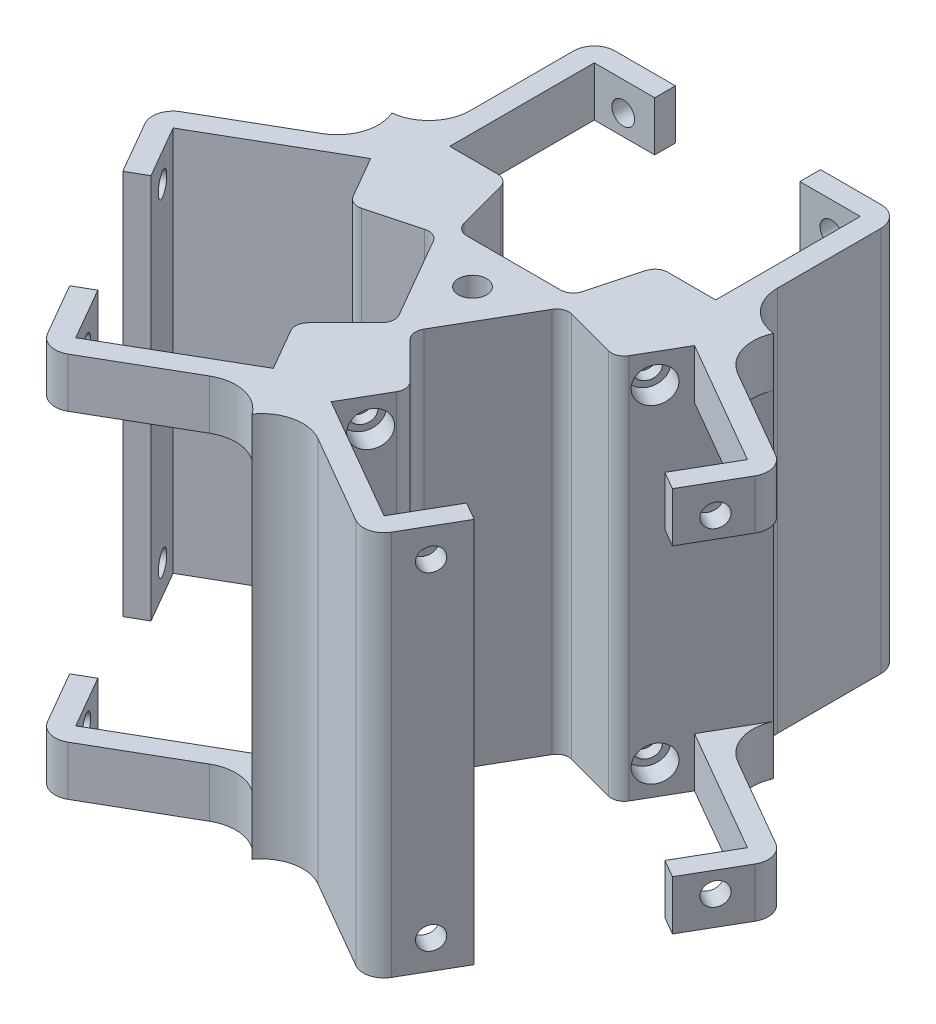
SolidWorks part; units mm, degrees
ref_plane "Alzado" through (0, 0, 0) normal (0, 0, 1) x (1, 0, 0)
ref_plane "Planta" through (0, 0, 0) normal (0, 1, 0) x (1, 0, 0)
ref_plane "Vista lateral" through (0, 0, 0) normal (1, 0, 0) x (0, 0, -1)
sketch "Croquis1" plane through (0, 0, 0) normal (0, 1, 0) x (1, 0, 0)
  line L0 (0, 50.8) -> (0, -50.8) construction
  line L1 (-50.8, 0) -> (50.8, 0) construction
  line L2 (0, 0) -> (-35.921, -35.921) construction
  line L3 (0, 0) -> (35.921, -35.921) construction
  line L10 (0, -17.5) -> (-15.1554, 8.75) construction
  line L11 (-15.1554, 8.75) -> (15.1554, 8.75) construction
  line L12 (15.1554, 8.75) -> (0, -17.5) construction
  line L13 (-1.2978, -16.7522) -> (-15.1813, 7.2027) construction
  line L14 (1.2978, -16.7522) -> (15.1813, 7.2027) construction
  line L15 (-13.8835, 9.4549) -> (13.8835, 9.4549) construction
  line L16 (1.6964, -16.0645) -> (13.335, -27.7031)
  line L17 (13.335, -27.7031) -> (0, -50.8)
  line L18 (0, -50.8) -> (-13.335, -27.7031)
  line L19 (-13.335, -27.7031) -> (-1.6964, -16.0645)
  line L20 (-17.3241, 25.4) -> (-13.0641, 9.5013)
  line L21 (-43.9941, 25.4) -> (-17.3241, 25.4)
  line L22 (-30.6591, 2.3031) -> (-43.9941, 25.4)
  line L23 (-14.7604, 6.5631) -> (-30.6591, 2.3031)
  line L24 (30.6591, 2.3031) -> (14.7604, 6.5631)
  line L25 (43.9941, 25.4) -> (30.6591, 2.3031)
  line L26 (17.3241, 25.4) -> (43.9941, 25.4)
  line L27 (13.0641, 9.5013) -> (17.3241, 25.4)
  line L28 (-14.7604, 6.5631) -> (-1.6964, -16.0645)
  line L29 (1.6964, -16.0645) -> (14.7604, 6.5631)
  line L30 (-13.0641, 9.5013) -> (13.0641, 9.5013)
  line L31 (-43.9941, 25.4) -> (0, -50.8) construction
  line L32 (43.9941, 25.4) -> (0, -50.8) construction
  line L33 (-43.9941, 25.4) -> (43.9941, 25.4) construction
  circle A0 centre (0, 0) radius 50.8 construction
  circle A7 centre (0, 0) radius 17.5 construction
  circle A8 centre (-13.8835, 7.9549) radius 1.5 construction
  circle A9 centre (13.8835, 7.9549) radius 1.5 construction
  circle A10 centre (0, -16) radius 1.5 construction
  arc A11 (-15.1813, 7.2027) -> (-13.8835, 9.4549) centre (-13.8835, 7.9549) cw construction
  arc A12 (15.1813, 7.2027) -> (13.8835, 9.4549) centre (13.8835, 7.9549) ccw construction
  arc A13 (1.2978, -16.7522) -> (-1.2978, -16.7522) centre (0, -16) cw construction
  arc A14 (-15.1813, 7.2027) -> (-13.8835, 9.4549) centre (-13.8835, 7.9549) cw construction
  arc A15 (13.8835, 9.4549) -> (15.1813, 7.2027) centre (13.8835, 7.9549) cw construction
  arc A16 (-1.2978, -16.7522) -> (1.2978, -16.7522) centre (0, -16) ccw construction
  circle A17 centre (0, 0) radius 76.2 construction
  point P45 (0, 0)
  dimension "D1" = 101.6
  dimension "D6" = 13.8835
  dimension "D9" = 3
  dimension "D5" = 3
  dimension "D4" = 35
  dimension "D10" = 152.4
  dimension "D2" = 45
  dimension "D3" = 45
  dimension "D7" = 26.67
extrude "Saliente-Extruir1" add sketch "Croquis1" along normal blind 88.9
sketch "Croquis4" plane through (0, 88.9, 0) normal (0, 1, 0) x (1, 0, 0)
  circle A0 centre (0, 0) radius 3.25
  dimension "D1" = 6.5
extrude "Cortar-Extruir1" cut sketch "Croquis4" against normal through all
fillet "Redondeo6" radius 3 5 edges at (-14.7604, 44.45, -6.5631) (1.6964, 44.45, 16.0645) (-1.6964, 44.45, 16.0645) (-13.0641, 44.45, -9.5013) (13.0641, 44.45, -9.5013)
fillet "Redondeo7" radius 3 6 edges at (-17.3241, 44.45, -25.4) (-30.6591, 44.45, -2.3031) (17.3241, 44.45, -25.4) (-13.335, 44.45, 27.7031) (30.6591, 44.45, -2.3031) (13.335, 44.45, 27.7031)
scale "Escala2" scale about centroid uniform scaling yes scale factor 1.05
sketch "Croquis9" plane through (0, 91.1225, 0) normal (0, 1, 0) x (1, 0, 0)
  line L9 (0, 76.2) -> (0, -76.2) construction
  line L10 (76.2, 0) -> (-76.2, 0) construction
  line L41 (-37.1934, 26.6702) -> (-37.1934, 61.6702)
  line L42 (-69.5041, -2.9545) -> (-39.1932, 14.5455)
  line L43 (-20.607, 26.6702) -> (-46.1934, 26.6702) construction
  line L44 (-32.1934, 66.6702) -> (-17.5643, 66.6702)
  line L45 (-17.5643, 66.6702) -> (-17.5643, 61.6702)
  line L46 (-17.5643, 61.6702) -> (-32.1934, 61.6702)
  line L47 (-32.1934, 61.6702) -> (-32.1934, 26.6702)
  line L48 (-32.1934, 26.6702) -> (-37.1934, 26.6702)
  line L49 (32.1934, 61.6702) -> (32.1934, 26.6702)
  line L50 (17.5643, 61.6702) -> (32.1934, 61.6702)
  line L51 (17.5643, 66.6702) -> (17.5643, 61.6702)
  line L52 (32.1934, 66.6702) -> (17.5643, 66.6702)
  line L53 (37.1934, 26.6702) -> (37.1934, 61.6702)
  line L54 (32.1934, 26.6702) -> (37.1934, 26.6702)
  line L55 (39.1937, 14.5452) -> (41.6937, 18.8753)
  line L56 (41.6937, 18.8753) -> (72.0046, 1.3753)
  line L57 (73.8347, -5.4548) -> (66.5202, -18.124)
  line L58 (66.5202, -18.124) -> (62.1901, -15.624)
  line L59 (62.1901, -15.624) -> (69.5046, -2.9548)
  line L60 (69.5046, -2.9548) -> (39.1937, 14.5452)
  line L61 (37.3112, -58.7154) -> (7.0003, -41.2154)
  line L62 (7.0003, -41.2154) -> (4.5003, -45.5455)
  line L63 (4.5003, -45.5455) -> (34.8112, -63.0455)
  line L64 (41.6414, -61.2154) -> (48.9559, -48.5462)
  line L65 (48.9559, -48.5462) -> (44.6258, -46.0462)
  line L66 (44.6258, -46.0462) -> (37.3112, -58.7154)
  line L79 (-39.1937, 14.5452) -> (-41.6937, 18.8753) [skipped]
  line L80 (-39.1932, 14.5455) -> (-41.6932, 18.8756)
  line L81 (-41.6937, 18.8753) -> (-72.0046, 1.3753) [skipped]
  line L83 (-41.6932, 18.8756) -> (-72.0041, 1.3756)
  line L85 (-69.5046, -2.9548) -> (-39.1937, 14.5452) [skipped]
  line L86 (-62.1901, -15.624) -> (-69.5046, -2.9548) [skipped]
  line L87 (-66.5202, -18.124) -> (-62.1901, -15.624) [skipped]
  line L88 (-73.8347, -5.4548) -> (-66.5202, -18.124) [skipped]
  line L89 (-73.8342, -5.4545) -> (-66.5197, -18.1237)
  line L90 (-66.5197, -18.1237) -> (-62.1896, -15.6237)
  line L91 (-62.1896, -15.6237) -> (-69.5041, -2.9545)
  line L92 (-46.1934, 26.6702) -> (-33.4002, 4.5117) construction
  line L93 (-7.0003, -41.2154) -> (-4.5003, -45.5455) [skipped]
  line L94 (-4.5003, -45.5455) -> (-34.8112, -63.0455) [skipped]
  line L95 (-41.6414, -61.2154) -> (-48.9559, -48.5462) [skipped]
  line L96 (-48.9559, -48.5462) -> (-44.6258, -46.0462) [skipped]
  line L97 (-44.6258, -46.0462) -> (-37.3112, -58.7154) [skipped]
  line L98 (-37.3112, -58.7154) -> (-7.0003, -41.2154) [skipped]
  line L99 (-6.9998, -41.2151) -> (-4.4998, -45.5452)
  line L100 (-4.4998, -45.5452) -> (-34.8107, -63.0452)
  line L101 (-41.6408, -61.2151) -> (-48.9554, -48.5459)
  line L102 (-48.9554, -48.5459) -> (-44.6253, -46.0459)
  line L103 (-44.6253, -46.0459) -> (-37.3107, -58.7151)
  line L104 (-37.3107, -58.7151) -> (-6.9998, -41.2151)
  line L105 (-12.7928, -31.1813) -> (0.0004, -53.3398) construction
  circle A0 centre (0, 0) radius 101.6 construction
  circle A1 centre (0, 0) radius 76.2 construction
  arc A8 (-37.1934, 61.6702) -> (-32.1934, 66.6702) centre (-32.1934, 61.6702) cw
  arc A9 (37.1934, 61.6702) -> (32.1934, 66.6702) centre (32.1934, 61.6702) ccw
  arc A10 (72.0046, 1.3753) -> (73.8347, -5.4548) centre (69.5046, -2.9548) cw
  arc A11 (34.8112, -63.0455) -> (41.6414, -61.2154) centre (37.3112, -58.7154) ccw
  arc A14 (-72.0046, 1.3753) -> (-73.8347, -5.4548) centre (-69.5046, -2.9548) ccw [skipped]
  arc A15 (-72.0041, 1.3756) -> (-73.8342, -5.4545) centre (-69.5041, -2.9545) ccw
  arc A16 (-34.8112, -63.0455) -> (-41.6414, -61.2154) centre (-37.3112, -58.7154) cw [skipped]
  arc A17 (-34.8107, -63.0452) -> (-41.6408, -61.2151) centre (-37.3107, -58.7151) cw
  point P55 (0.0002, 0.0003)
  point P56 (-1.3626, -0.7865)
  point P58 (0, 0)
  point P61 (0.0002, 0.0003)
  dimension "D1" = 152.4
  dimension "D2" = 203.2
  dimension "D3" = 5
  dimension "D9" = 2
  dimension "D4" = 9
  dimension "D5" = 35
  dimension "D6" = 3
  dimension "D7" = 2
sketch "Croquis12" plane through (0, 91.1225, 0) normal (0, 1, 0) x (1, 0, 0)
  line L0 (0, 101.6) -> (0, -101.6) construction
  circle A0 centre (0, 0) radius 76.2 construction
  circle A1 centre (0, 0) radius 101.6 construction
  dimension "D1" = 152.4
  dimension "D2" = 203.2
extrude "Saliente-Extruir2" add sketch "Croquis9" against normal through all
sketch "Croquis14" plane through (0, 0, -66.6702) normal (0, 0, -1) x (-1, 0, 0)
  line L0 (-32.1934, -2.2225) -> (-32.1934, 91.1225) construction
  line L1 (17.5643, 91.1225) -> (32.1934, 91.1225) construction
  circle A0 centre (25.1934, 84.1225) radius 2.75
  circle A1 centre (25.1934, 4.7775) radius 2.75
  circle A2 centre (-25.1934, 4.7775) radius 2.75
  circle A3 centre (-25.1934, 84.1225) radius 2.75
  dimension "D1" = 5.5
  dimension "D2" = 7
  dimension "D3" = 7
  dimension "D4" = 7
  dimension "D5" = 7
  dimension "D6" = 7
  dimension "D7" = 7
extrude "Cortar-Extruir2" cut sketch "Croquis14" against normal blind 10
sketch "Croquis15" plane through (0, 0, -26.6702) normal (0, 0, -1) x (-1, 0, 0)
  line L0 (32.1934, -2.2225) -> (32.1934, 91.1225) construction
  line L1 (-32.1934, -2.2225) -> (-20.6078, -2.2225) construction
  line L2 (-32.1934, 91.1225) -> (-20.6078, 91.1225) construction
  circle A0 centre (-25.1934, 4.7775) radius 4.25
  circle A1 centre (25.1934, 4.7775) radius 4.25
  circle A2 centre (-25.1934, 84.1225) radius 4.25
  circle A3 centre (25.1934, 84.1225) radius 4.25
  dimension "D1" = 8.5
  dimension "D2" = 7
  dimension "D3" = 7
  dimension "D4" = 7
  dimension "D5" = 7
  dimension "D6" = 7
  dimension "D7" = 7
extrude "Cortar-Extruir3" cut sketch "Croquis15" against normal blind 5.5
sketch "Croquis16" plane through (0, 0, -21.1702) normal (0, 0, -1) x (-1, 0, 0)
  circle A0 centre (-25.1934, 4.7775) radius 2.775
  circle A1 centre (25.1934, 4.7775) radius 2.775
  circle A2 centre (25.1934, 84.1225) radius 2.775
  circle A3 centre (-25.1934, 84.1225) radius 2.775
  dimension "D1" = 5.55
extrude "Cortar-Extruir4" cut sketch "Croquis16" against normal blind 3
pattern_circular "MatrizC7" count 3 over 360 about axis through (0.0004, -2.2225, -0.0002) along (0, 1, 0) of "Cortar-Extruir4", "Cortar-Extruir3"
sketch "Croquis17" plane through (18.5967, 0, -32.2104) normal (0.5, 0, -0.866) x (-0.866, 0, -0.5)
  line L0 (-26.6703, 91.1225) -> (-26.6703, -2.2225) construction
  line L1 (-26.6703, 79.1225) -> (-68.6703, 79.1225)
  line L2 (-26.6703, 79.1225) -> (-26.6703, 9.7775)
  line L3 (-26.6703, 9.7775) -> (-68.6703, 9.7775)
  line L4 (-68.6703, 79.1225) -> (-68.6703, 9.7775)
  line L5 (76.2, 91.1225) -> (-76.2, 91.1225) construction
  line L6 (-61.6702, -2.2225) -> (-26.6703, -2.2225) construction
  dimension "D1" = 42
  dimension "D2" = 12
  dimension "D3" = 12
extrude "Cortar-Extruir5" cut sketch "Croquis17" against normal blind 31
sketch "Croquis18" plane through (-37.1934, 0, 0) normal (-1, 0, 0) x (0, 0, 1)
  line L0 (-26.6702, 91.1225) -> (-26.6702, -2.2225) construction
  line L1 (-26.6702, 79.1225) -> (-71.6702, 79.1225)
  line L2 (-26.6702, 79.1225) -> (-26.6702, 9.7775)
  line L3 (-26.6702, 9.7775) -> (-71.6702, 9.7775)
  line L4 (-71.6702, 79.1225) -> (-71.6702, 9.7775)
  line L5 (101.6, 91.1225) -> (-101.6, 91.1225) construction
  line L6 (-61.6702, -2.2225) -> (-26.6702, -2.2225) construction
  dimension "D1" = 12
  dimension "D2" = 12
  dimension "D3" = 45
extrude "Cortar-Extruir6" cut sketch "Croquis18" against normal blind 31
fillet "Redondeo8" radius 10 2 edges at (-37.1934, 85.1225, -26.6702) (-37.1934, 3.7775, -26.6702)
fillet "Redondeo9" radius 10 1 edges at (37.1934, 44.45, -26.6702)
fillet "Redondeo12" radius 10 1 edges at (4.5004, 44.45, 45.5456)
fillet "Redondeo13" radius 10 2 edges at (41.6938, 85.1225, -18.8753) (41.6938, 3.7775, -18.8753)
pattern_circular "MatrizC8" count 3 over 360 about axis through (0.0004, 91.1225, -0.0002) along (0, 1, 0) of "Cortar-Extruir6"
fillet "Redondeo14" radius 10 2 edges at (-4.4998, 3.7775, 45.5452) (-4.4998, 85.1225, 45.5452)
fillet "Redondeo16" radius 10 1 edges at (-41.6932, 44.45, -18.8756)
fillet "Redondeo17" radius 3 1 edges at (15.4988, 44.45, -6.8915)
sketch "Croquis20" plane through (-57.7375, 0, 33.3348) normal (-0.866, 0, 0.5) x (0.5, 0, 0.866)
  line L0 (32.1934, -2.2225) -> (32.1934, 9.7775) construction
  line L1 (-87.9882, 91.1225) -> (87.9882, 91.1225) construction
  circle A0 centre (25.1934, 4.7775) radius 2.78
  circle A1 centre (25.1934, 84.1225) radius 2.78
  circle A2 centre (-25.1934, 84.1225) radius 2.78
  circle A3 centre (-25.1934, 4.7775) radius 2.78
  dimension "D1" = 5.56
  dimension "D2" = 7
  dimension "D3" = 7
  dimension "D4" = 7
  dimension "D5" = 7
extrude "Cortar-Extruir7" cut sketch "Croquis20" against normal blind 10
sketch "Croquis21" plane through (57.7381, 0, 33.3351) normal (0.866, 0, 0.5) x (0.5, 0, -0.866)
  line L0 (17.5643, 91.1225) -> (32.1934, 91.1225) construction
  line L1 (-32.1934, -2.2225) -> (-32.1934, 91.1225) construction
  line L2 (-32.1934, -2.2225) -> (-17.5643, -2.2225) construction
  circle A0 centre (25.1934, 4.7775) radius 2.775
  circle A1 centre (25.1934, 84.1225) radius 2.775
  circle A2 centre (-25.1934, 84.1225) radius 2.775
  circle A3 centre (-25.1934, 4.7775) radius 2.775
  dimension "D1" = 5.55
  dimension "D2" = 7
  dimension "D3" = 7
  dimension "D4" = 7
  dimension "D5" = 7
extrude "Cortar-Extruir8" cut sketch "Croquis21" against normal blind 10
